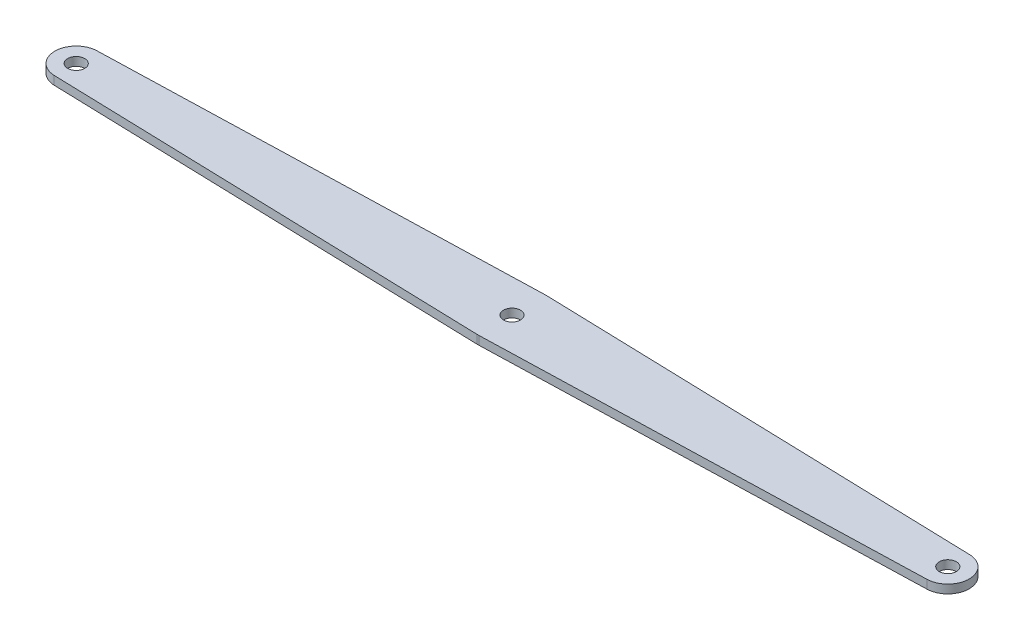
SolidWorks part; units mm, degrees
ref_plane "Спереди" through (0, 0, 0) normal (0, 0, 1) x (1, 0, 0)
ref_plane "Сверху" through (0, 0, 0) normal (0, 1, 0) x (1, 0, 0)
ref_plane "Справа" through (0, 0, 0) normal (1, 0, 0) x (0, 0, -1)
sketch "Эскиз1" plane through (0, 0, 0) normal (0, 1, 0) x (1, 0, 0)
  line L0 (-102, 0) -> (102, 0) construction
  line L1 (-102.1471, 4.9978) -> (-0.2353, 7.9965)
  line L2 (-102.1471, -4.9978) -> (-0.2353, -7.9965)
  line L3 (0.2353, 7.9965) -> (102.1471, 4.9978)
  line L4 (-0.2353, -7.9965) -> (0.2353, -7.9965)
  line L5 (102.1471, -4.9978) -> (0.2353, -7.9965)
  line L6 (-0.2353, 7.9965) -> (0.2353, 7.9965)
  arc A0 (0.2353, 7.9965) -> (-0.2353, 7.9965) centre (0, 0) ccw construction
  arc A1 (-102.1471, 4.9978) -> (-102.1471, -4.9978) centre (-102, 0) ccw
  arc A2 (102.1471, -4.9978) -> (102.1471, 4.9978) centre (102, 0) ccw
  arc A3 (-0.2353, -7.9965) -> (0.2353, -7.9965) centre (0, 0) ccw construction
  point P7 (0, 0)
  dimension "D2" = 8
  dimension "D3" = 5
  dimension "D1" = 204
extrude "тело" add sketch "Эскиз1" along normal blind 2
sketch "Эскиз2" plane through (0, 2, 0) normal (0, 1, 0) x (1, 0, 0)
  circle A0 centre (0, 0) radius 2
  dimension "D1" = 4
extrude "отверстие под ось вращения" cut sketch "Эскиз2" against normal through all
sketch "Эскиз3" plane through (0, 2, 0) normal (0, 1, 0) x (1, 0, 0)
  circle A0 centre (-102, 0) radius 2
  circle A1 centre (102, 0) radius 2
  dimension "D1" = 4
extrude "отверстие для крепления тягов" cut sketch "Эскиз3" against normal through all
